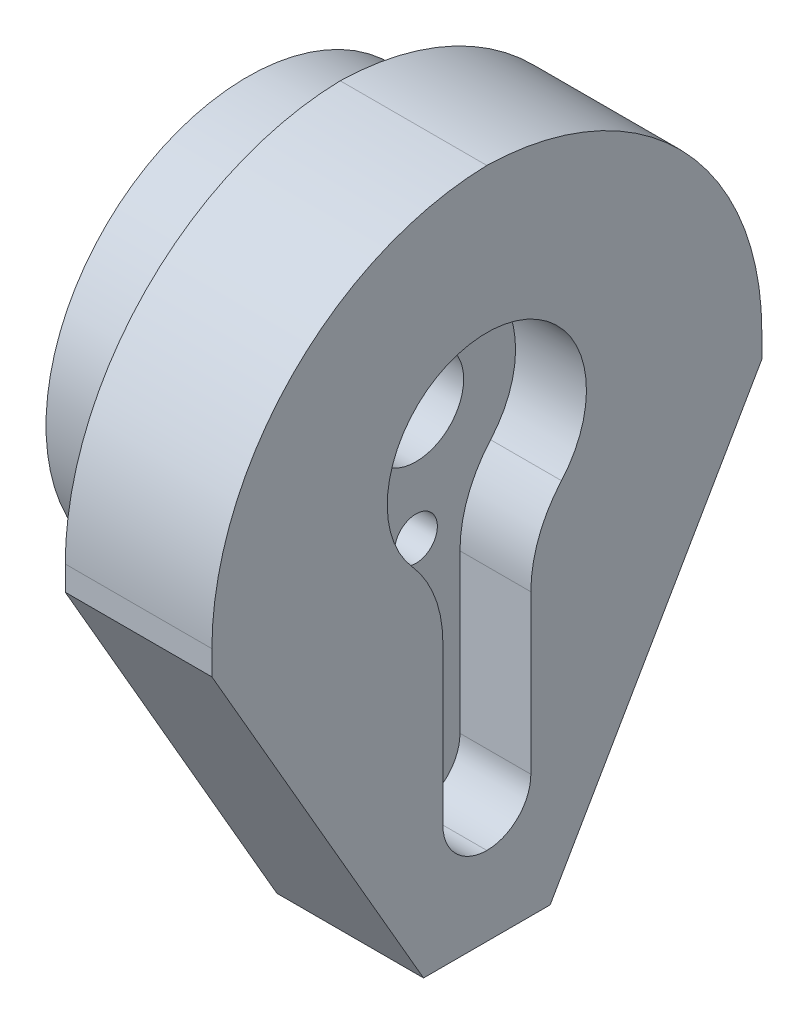
SolidWorks part; units mm, degrees
ref_plane "Front Plane" through (0, 0, 0) normal (0, 0, 1) x (1, 0, 0)
ref_plane "Top Plane" through (0, 0, 0) normal (0, 1, 0) x (1, 0, 0)
ref_plane "Right Plane" through (0, 0, 0) normal (1, 0, 0) x (0, 0, -1)
sketch "Sketch1" plane through (0, 0, 0) normal (1, 0, 0) x (0, 0, -1)
  line L1 (-10, 10) -> (10, 10)
  line L2 (-10, 10) -> (-10, -10)
  line L3 (-10, -10) -> (10, -10)
  line L4 (10, 10) -> (10, -10)
  line L5 (-10, 10) -> (10, -10) construction
  line L6 (-10, -10) -> (10, 10) construction
  point P0 (0, 0)
  dimension "D1" = 20
  dimension "D2" = 20
extrude "Boss-Extrude1" add sketch "Sketch1" along normal blind 20
sketch "Sketch2" plane through (20, 0, 0) normal (1, 0, 0) x (0, 0, -1)
  line L1 (-22.5, 35) -> (22.5, 35)
  line L2 (-22.5, 35) -> (-22.5, -35)
  line L3 (-22.5, -35) -> (22.5, -35)
  line L4 (22.5, 35) -> (22.5, -35)
  line L5 (-22.5, 35) -> (22.5, -35) construction
  line L6 (-22.5, -35) -> (22.5, 35) construction
  point P0 (0, 0)
  dimension "D1" = 45
  dimension "D2" = 70
extrude "Boss-Extrude2" add sketch "Sketch2" along normal blind 12
sketch "Sketch4" plane through (32, 0, 0) normal (1, 0, 0) x (0, 0, -1)
  line L0 (0, 7.65) -> (0, 8.1702) construction
  line L1 (7.65, 7.65) -> (-7.65, 7.65) construction
  line L17 (3.6, -26.55) -> (-3.6, -26.55) construction
  line L18 (-7.65, 7.65) -> (7.65, 7.65) construction
  line L22 (-7.65, 7.65) -> (-7.65, -27.55) construction
  line L23 (-7.65, -27.55) -> (7.65, -27.55) construction
  line L24 (7.65, 7.65) -> (7.65, -27.55) construction
  line L25 (-7.65, 7.65) -> (7.65, -27.55) construction
  line L26 (-7.65, -27.55) -> (7.65, 7.65) construction
  line L27 (3.6, -26.55) -> (3.6, -28.55) construction
  line L28 (3.6, -28.55) -> (-3.6, -28.55) construction
  line L29 (-3.6, -26.55) -> (-3.6, -28.55) construction
  line L30 (3.6, -26.55) -> (-3.6, -28.55) construction
  line L31 (3.6, -28.55) -> (-3.6, -26.55) construction
  line L34 (3.6, -28.55) -> (-3.6, -28.55)
  line L35 (-3.6, -28.55) -> (-3.6, -7.3118)
  line L36 (3.6, -28.55) -> (3.6, -7.3118)
  arc A1 (3.6, -6.75) -> (-3.6, -6.75) centre (0, 0) ccw construction
  arc A2 (3.6, -7.3118) -> (-3.6, -7.3118) centre (0, 0) ccw
  point P1 (0, -27.55)
  point P7 (0, -13.75)
  point P10 (0, 7.65)
  point P14 (0, -9.95)
  dimension "D1" = 15.3
  dimension "D5" = 2
  dimension "D2" = 15.3
  dimension "D3" = 35.2
  dimension "D4" = 7.2
extrude "Cut-Extrude1" cut sketch "Sketch4" against normal blind 5.8
fillet "Fillet1" radius 3.6 2 edges at (29.1, -28.55, 3.6) (29.1, -28.55, -3.6)
fillet "Fillet2" radius 10 2 edges at (29.1, -7.3118, 3.6) (29.1, -7.3118, -3.6)
sketch "Sketch5" plane through (0, 0, 0) normal (-1, 0, 0) x (0, 0, 1)
  circle A0 centre (0, 0) radius 3.9
  dimension "D1" = 7.8
extrude "Cut-Extrude2" cut sketch "Sketch5" against normal through all
sketch "Sketch6" plane through (26.2, 0, 0) normal (1, 0, 0) x (0, 0, -1)
  line L0 (0, -19.35) -> (0, 0) construction
  line L1 (0, -25.65) -> (0, -23.15) construction
  line L2 (0, -23.15) -> (0, -21.85) construction
  line L3 (0, -21.85) -> (0, -19.35) construction
  line L5 (0, 0) -> (1.164, 0) construction
  line L6 (0, 0) -> (0, -9.35) construction
  line L7 (0, -9.35) -> (1.164, -9.35) construction
  line L8 (1.164, 0) -> (1.164, -9.35) construction
  line L9 (0, 0) -> (1.164, -9.35) construction
  line L10 (0, -9.35) -> (1.164, 0) construction
  circle A0 centre (0, -20.6) radius 1.75
  circle A1 centre (0, -9.35) radius 1.75
  point P11 (0.582, -4.675)
  dimension "D5" = 3.5
  dimension "D6" = 9.35
  dimension "D7" = 3.5
  dimension "D1" = 19.35
  dimension "D2" = 2.5
  dimension "D3" = 1.3
  dimension "D4" = 2.5
extrude "Cut-Extrude3" cut sketch "Sketch6" against normal up to next
sketch "Sketch13" plane through (0, 0, 0) normal (-1, 0, 0) x (0, 0, 1)
  line L1 (-10, 10) -> (10, 10)
  line L2 (-10, 10) -> (-10, -10)
  line L3 (-10, -10) -> (10, -10)
  line L4 (10, 10) -> (10, -10)
extrude "Cut-Extrude9" cut sketch "Sketch13" against normal up to surface (20 mm away) up to face at (20, -20.6, -1.75)
sketch "Sketch14" plane through (20, 0, 0) normal (-1, 0, 0) x (0, 0, 1)
  line L0 (0, -11.1) -> (0, -18.85) construction
  circle A0 centre (0, -9.35) radius 1.75 construction
  circle A1 centre (0, -20.6) radius 1.75 construction
  circle A3 centre (0, 0) radius 16.475
  point P7 (0, -14.975)
extrude "Boss-Extrude3" add sketch "Sketch14" along normal blind 7.6 contours A3
sketch "Sketch15" plane through (0, 35, 0) normal (0, 1, 0) x (1, 0, 0)
  line L1 (20, 22.5) -> (32, 22.5)
  line L2 (20, 22.5) -> (20, -22.5)
  line L3 (20, -22.5) -> (32, -22.5)
  line L4 (32, 22.5) -> (32, -22.5)
extrude "Cut-Extrude10" cut sketch "Sketch15" against normal blind 15
fillet "Fillet3" radius 23 2 edges at (26, 20, -22.5) (26, 20, 22.5)
chamfer "Chamfer1" distance 30 angle 30 1 edges at (26, -35, 22.5) first distance on face at (26, -19, 22.5)
chamfer "Chamfer2" distance 30 angle 30 1 edges at (26, -35, -22.5) first distance on face at (26, -19, -22.5)
sketch "Sketch16" plane through (12.4, 0, 0) normal (-1, 0, 0) x (0, 0, 1)
  circle A4 centre (0, 0) radius 13.475
  circle A5 centre (0, 0) radius 13.475
  dimension "D1" = 3
extrude "Cut-Extrude11" cut sketch "Sketch16" against normal blind 7.6
fillet "Fillet4" radius 1 2 edges at (20, 0, 13.475) (20, 0, -16.475)
